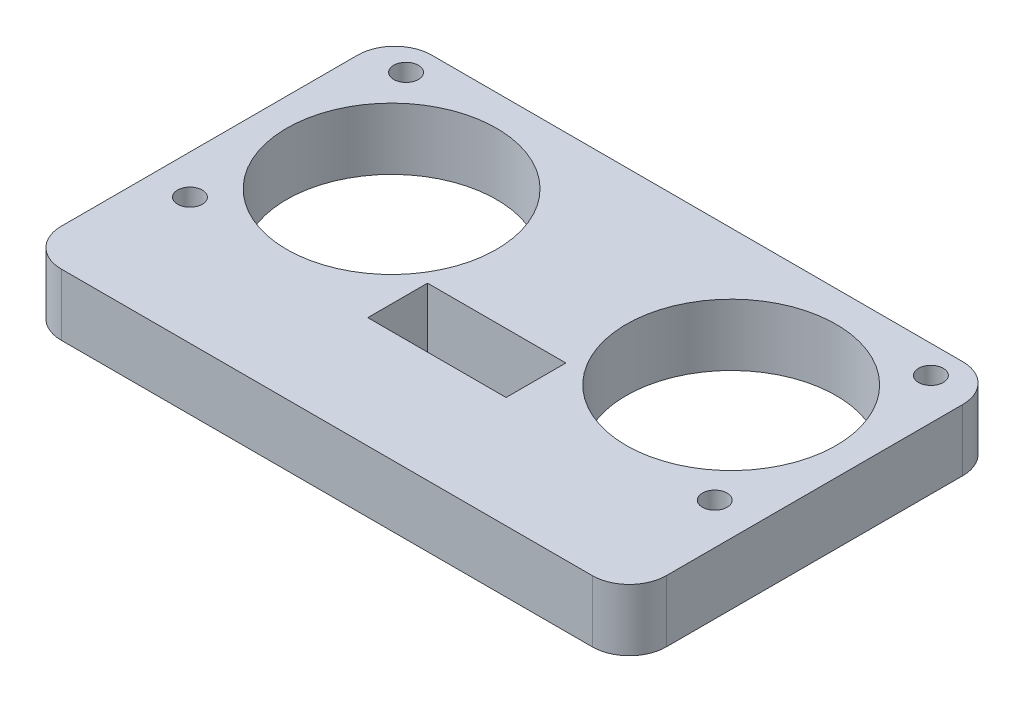
SolidWorks part; units mm, degrees
ref_plane "Front Plane" through (0, 0, 0) normal (0, 0, 1) x (1, 0, 0)
ref_plane "Top Plane" through (0, 0, 0) normal (0, 1, 0) x (1, 0, 0)
ref_plane "Right Plane" through (0, 0, 0) normal (1, 0, 0) x (0, 0, -1)
sketch "Sketch1" plane through (0, 0, 0) normal (0, 1, 0) x (1, 0, 0)
  circle A0 centre (0, 0) radius 20
  circle A1 centre (0, 0) radius 21
  dimension "D1" = 40
  dimension "D2" = 42
extrude "Boss-Extrude1" add sketch "Sketch1" along normal blind 3.5
ref_plane "Plane1" through (0, 3.5, 0) normal (0, 1, 0) x (1, 0, 0)
sketch "Sketch2" plane through (0, 3.5, 0) normal (0, 1, 0) x (1, 0, 0)
  line L0 (-23.55, 0) -> (23.55, 0) construction
  line L1 (-29, -29) -> (29, -29)
  line L2 (-29, -29) -> (-29, 29)
  line L3 (-29, 29) -> (29, 29)
  line L4 (29, -29) -> (29, 29)
  line L5 (-29, -29) -> (29, 29) construction
  line L6 (-29, 29) -> (29, -29) construction
  line L7 (-28.2, -28.2) -> (28.2, -28.2) construction
  line L8 (-28.2, -28.2) -> (-28.2, 28.2) construction
  line L9 (-28.2, 28.2) -> (28.2, 28.2) construction
  line L10 (28.2, -28.2) -> (28.2, 28.2) construction
  line L11 (-28.2, -28.2) -> (28.2, 28.2) construction
  line L12 (-28.2, 28.2) -> (28.2, -28.2) construction
  line L13 (-23.55, 28.2) -> (-23.55, 23.55) construction
  line L14 (-23.55, 23.55) -> (-28.2, 23.55) construction
  line L15 (0, 28.2) -> (0, -28.2) construction
  line L16 (0, 29) -> (0, 49) construction
  line L17 (-22.5, 49) -> (22.5, 49) construction
  line L18 (-22.5, 49) -> (-22.5, 29) construction
  line L19 (22.5, 49) -> (22.5, 29) construction
  line L20 (0, 49) -> (0, 48) construction
  line L21 (-4.9, 48) -> (4.9, 48) construction
  line L22 (-4.9, 48) -> (-4.9, 44.56) construction
  line L23 (-4.9, 44.56) -> (4.9, 44.56) construction
  line L24 (4.9, 44.56) -> (4.9, 48) construction
  line L25 (-24.5, 29) -> (-24.5, 51)
  line L26 (-24.5, 51) -> (24.5, 51)
  line L27 (24.5, 51) -> (24.5, 29)
  line L28 (-13.76, 39) -> (13.76, 39) construction
  line L29 (-5.6, 48.7) -> (5.6, 48.7)
  line L31 (5.6, 43.86) -> (-5.6, 43.86)
  line L32 (-5.6, 43.86) -> (-5.6, 48.7)
  line L33 (5.6, 43.86) -> (5.6, 48.7)
  line L34 (-24.5, 51) -> (-24.5, 59)
  line L35 (-24.5, 59) -> (24.5, 59)
  line L36 (24.5, 59) -> (24.5, 51)
  line L37 (0, 0) -> (34, 0) construction
  line L38 (29, 5) -> (39, 5)
  line L39 (29, -5) -> (39, -5)
  line L40 (39, 5) -> (39, -5)
  line L41 (-29, -5) -> (-39, -5)
  line L42 (-39, 5) -> (-39, -5)
  line L43 (-29, 5) -> (-39, 5)
  circle A0 centre (-23.55, 23.55) radius 2.55 construction
  circle A1 centre (23.55, 23.55) radius 2.55 construction
  circle A2 centre (23.55, -23.55) radius 2.55 construction
  circle A3 centre (-23.55, -23.55) radius 2.55 construction
  circle A4 centre (0, 0) radius 5.5563 construction
  circle A5 centre (13.76, 39) radius 7.5 construction
  circle A6 centre (-13.76, 39) radius 7.5 construction
  circle A7 centre (-13.76, 39) radius 8.5
  circle A8 centre (13.76, 39) radius 8.5
  circle A9 centre (0, 0) radius 6.55
  circle A10 centre (-23.55, 23.55) radius 3.55
  circle A11 centre (23.55, 23.55) radius 3.55
  circle A12 centre (23.55, -23.55) radius 3.55
  circle A13 centre (-23.55, -23.55) radius 3.55
  circle A14 centre (34, 0) radius 2.55
  circle A15 centre (-34, 0) radius 2.55
  point P0 (0, 0)
  point P5 (0, 0)
  point P15 (0, 0)
  point P34 (0, 49)
  point P40 (0, 48)
  point P49 (0, 39)
  point P56 (0, 43.86)
  point P59 (0, 48.7)
  point P70 (34, 0)
  dimension "D4" = 5.1
  dimension "D5" = 11.1125
  dimension "D15" = 15
  dimension "D16" = 17
  dimension "D17" = 0.7
  dimension "D20" = 13.1
  dimension "D21" = 7.1
  dimension "D22" = 8
  dimension "D24" = 5.1
  dimension "D25" = 5
  dimension "D1" = 58
  dimension "D2" = 56.4
  dimension "D3" = 47.1
  dimension "D6" = 20
  dimension "D7" = 45
  dimension "D8" = 1
  dimension "D9" = 9.8
  dimension "D10" = 3.44
  dimension "D11" = 2
  dimension "D12" = 2
  dimension "D13" = 2
  dimension "D14" = 27.52
  dimension "D18" = 0.7
  dimension "D19" = 0.7
  dimension "D23" = 34
  dimension "D26" = 5
extrude "Boss-Extrude2" add sketch "Sketch2" along normal blind 5 contours L1 L4 L3 L2 A4 A1 A0 A2 A3 | L27 L26 L25 L3 A8 A7 L33 L31 L32 L29 | L40 L38 L4 L39 A14 | L2 L43 L42 L41 A15 region at (-28.1798, 3.5, 17) region at (-34, 3.5, 4.8586) region at (29.1414, 3.5, 0) region at (0, 3.5, -40.1992)
sketch "Sketch3" plane through (0, 3.5, 0) normal (0, 1, 0) x (1, 0, 0)
  line L0 (-5.6, 48.7) -> (5.6, 48.7)
  line L1 (5.6, 48.7) -> (5.6, 43.86)
  line L2 (5.6, 43.86) -> (-5.6, 43.86)
  line L3 (-5.6, 43.86) -> (-5.6, 48.7)
  line L4 (-13.76, 47.5) -> (-13.76, 30.5) construction
  line L5 (13.76, 47.5) -> (13.76, 30.5) construction
  line L6 (-24.5, 29) -> (24.5, 29)
  line L7 (24.5, 29) -> (24.5, 51)
  line L8 (24.5, 51) -> (-24.5, 51)
  line L9 (-24.5, 51) -> (-24.5, 29)
  line L10 (-24.5, 51) -> (-24.5, 59)
  line L11 (-24.5, 59) -> (24.5, 59)
  line L12 (24.5, 59) -> (24.5, 51)
  circle A0 centre (-13.76, 39) radius 8.5 construction
  circle A1 centre (-13.76, 39) radius 8.5
  circle A2 centre (13.76, 39) radius 8.5 construction
  circle A3 centre (13.76, 39) radius 8.5
  dimension "D1" = 8
sketch "Sketch4" plane through (0, 3.5, 0) normal (0, 1, 0) x (1, 0, 0)
  line L4 (-5.6791, 42.84) -> (-5.6791, 38)
  line L5 (5.5209, 38) -> (5.5209, 42.84)
  line L10 (-24.5, 29) -> (-24.5, 37)
  line L11 (-24.5, 51) -> (-24.5, 29) construction
  line L12 (24.5, 29) -> (24.5, 37)
  line L13 (24.5, 29) -> (24.5, 51) construction
  line L14 (-24.5, 37) -> (-24.5, 59)
  line L15 (24.5, 37) -> (24.5, 59)
  line L16 (-24.5, 59) -> (24.5, 59)
  line L17 (-24.5, 37) -> (24.5, 37)
  line L18 (0, 59) -> (0, 37) construction
  line L23 (-5.6791, 38) -> (5.5209, 38)
  line L24 (5.5209, 42.84) -> (-5.6791, 42.84)
  line L25 (-5.6791, 58) -> (5.5209, 58) construction
  line L26 (5.5209, 58) -> (5.5209, 53.16) construction
  line L27 (5.5209, 53.16) -> (-5.6791, 53.16) construction
  line L28 (-5.6791, 53.16) -> (-5.6791, 58) construction
  line L29 (-13.75, 56.5) -> (-13.75, 39.5) construction
  line L30 (-13.75, 48) -> (13.75, 48) construction
  circle A4 centre (-13.75, 48) radius 8.5
  circle A5 centre (13.75, 48) radius 8.5
  point P53 (0, 48)
  dimension "D2" = 17
  dimension "D1" = 8
  dimension "D3" = 22
  dimension "D4" = 1
  dimension "D5" = 5.5209
  dimension "D6" = 11.2
  dimension "D7" = 4.84
  dimension "D8" = 27.5
extrude "Ignore" add sketch "Sketch3" along normal blind 5 contours L3 L2 L1 L0 | L12 L11 L10 L8 | A3 | A1 region at (0, 3.5, -46.28) region at (0, 3.5, -55) region at (-13.76, 3.5, -39) region at (13.76, 3.5, -39)
extrude "Cut-Extrude2" cut sketch "Sketch4" along normal through all contours A4 | A5 | L28 L27 L26 L25 | L5 L24 L4 L23 region at (-0.0791, 3.5, -40.42) region at (-13.75, 3.5, -48) region at (13.75, 3.5, -48)
fillet "Fillet1" radius 3 10 edges at (29, 6, -29) (39, 6, 5) (39, 6, -5) (29, 6, 29) (-29, 6, 29) (-39, 6, 5) (-39, 6, -5) (-29, 6, -29) (24.5, 6, -59) (-24.5, 6, -59)
sketch "Sketch5" plane through (0, 0, 0) normal (0, 0, 1) x (1, 0, 0)
  line L0 (-21, 3.5) -> (21, 3.5)
  line L1 (21, 3.5) -> (21, 0)
  line L2 (21, 0) -> (-21, 0)
  line L3 (-21, 0) -> (-21, 3.5)
extrude "Cut-Extrude3" cut sketch "Sketch5" against normal mid plane 50
sketch "Sketch6" plane through (0, 8.5, 0) normal (0, 1, 0) x (1, 0, 0)
  line L0 (-26, 29) -> (24.5, 29)
  line L1 (24.5, 29) -> (43.3219, 29)
  line L2 (43.3219, 29) -> (43.3219, -33.143)
  line L5 (-38.2971, 29) -> (-26, 29)
  line L6 (43.3219, -33.143) -> (-52.0728, -33.143)
  line L7 (-52.0728, -33.143) -> (-52.0728, 29)
  line L8 (-52.0728, 29) -> (-38.2971, 29)
extrude "Cut-Extrude5" cut sketch "Sketch6" against normal blind 10
fillet "Fillet2" radius 3 2 edges at (24.5, 6, -29) (-24.5, 6, -29)
sketch "Sketch8" plane through (0, 3.5, 0) normal (0, -1, 0) x (1, 0, 0)
  line L0 (-22.25, -48) -> (22.25, -48) construction
  line L1 (-0.0791, -42.84) -> (-0.0791, -54.7233) construction
  line L2 (5.5209, -42.84) -> (-5.6791, -42.84) construction
  line L4 (-22.6, -58.1) -> (22.6, -58.1)
  line L5 (-22.6, -58.1) -> (-22.6, -37.9)
  line L6 (-22.6, -37.9) -> (22.6, -37.9)
  line L7 (22.6, -58.1) -> (22.6, -37.9)
  line L8 (-22.6, -58.1) -> (22.6, -37.9) construction
  line L9 (-22.6, -37.9) -> (22.6, -58.1) construction
  circle A0 centre (-13.75, -48) radius 8.5 construction
  circle A1 centre (13.75, -48) radius 8.5 construction
  circle A2 centre (21.1709, -39.25) radius 1
  circle A3 centre (21.1709, -56.75) radius 1
  circle A4 centre (-21.3291, -56.75) radius 1
  circle A5 centre (-21.3291, -39.25) radius 1
  point P18 (0, -48)
  dimension "D2" = 2
  dimension "D3" = 8.75
  dimension "D1" = 44.5
  dimension "D4" = 8.75
  dimension "D5" = 42.5
  dimension "D6" = 42.5
  dimension "D7" = 20.2
  dimension "D8" = 45.2
extrude "Cut-Extrude6" cut sketch "Sketch8" against normal blind 20 contours A5 | A4 | A3 | A2 region at (21.1709, 3.5, -39.25) region at (21.1709, 3.5, -56.75) region at (-21.3291, 3.5, -56.75) region at (-21.3291, 3.5, -39.25)
